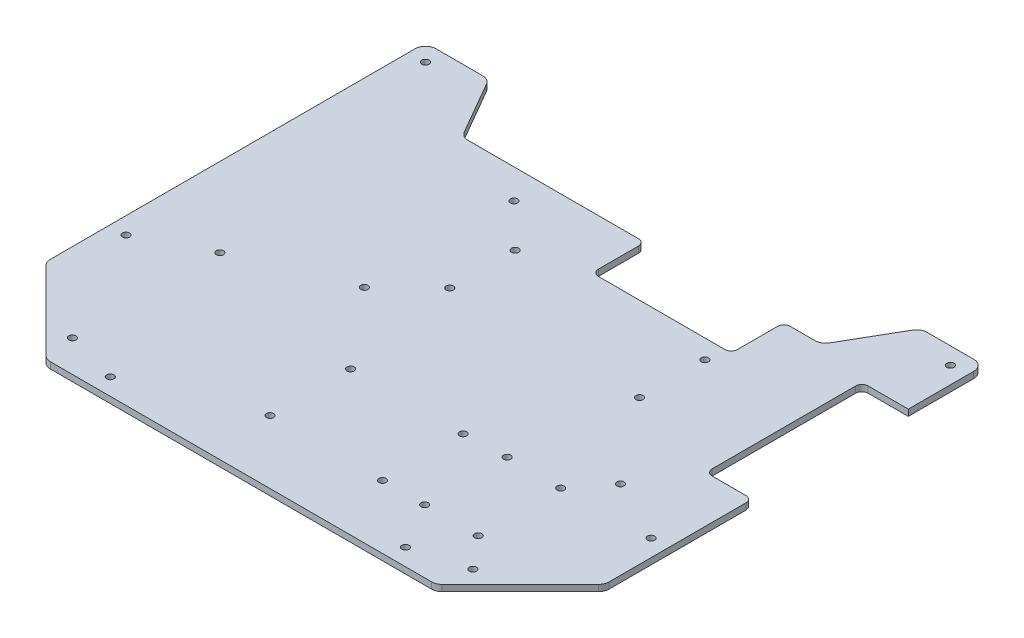
SolidWorks part; units mm, degrees
material "Acier non allié"
ref_plane "Front" through (0, 0, 0) normal (0, 0, 1) x (1, 0, 0)
ref_plane "Top" through (0, 0, 0) normal (0, 1, 0) x (1, 0, 0)
ref_plane "Right" through (0, 0, 0) normal (1, 0, 0) x (0, 0, -1)
sketch "Esquisse1" plane through (0, 0, 0) normal (0, 1, 0) x (1, 0, 0)
  line L0 (0, 0) -> (0, 190) construction
  line L1 (-92.5, 0) -> (92.5, 0)
  line L2 (92.5, 0) -> (132.5, 40)
  line L3 (132.5, 40) -> (132.5, 220)
  line L4 (132.5, 220) -> (102.5, 220)
  line L5 (102.5, 220) -> (85.1795, 190)
  line L6 (85.1795, 190) -> (-85.1795, 190)
  line L7 (-102.5, 220) -> (-85.1795, 190)
  line L8 (-132.5, 220) -> (-102.5, 220)
  line L9 (-132.5, 40) -> (-132.5, 220)
  line L10 (-92.5, 0) -> (-132.5, 40)
  dimension "D1" = 132.5
  dimension "D2" = 220
  dimension "D3" = 60
  dimension "D4" = 30
  dimension "D5" = 40
  dimension "D6" = 40
  dimension "D7" = 30
extrude "Boss.-Extru.1" add sketch "Esquisse1" along normal blind 3
fillet "Congé1" radius 5 10 edges at (92.5, 1.5, 0) (132.5, 1.5, -40) (132.5, 1.5, -220) (102.5, 1.5, -220) (85.1795, 1.5, -190) (-85.1795, 1.5, -190) (-102.5, 1.5, -220) (-132.5, 1.5, -220) (-92.5, 1.5, 0) (-132.5, 1.5, -40)
sketch "Esquisse2" plane through (0, 3, 0) normal (0, 1, 0) x (1, 0, 0)
  line L0 (0, 0) -> (0, 294.1173) construction
  line L2 (-90.4289, 0) -> (90.4289, 0) construction
  circle A0 centre (70, 8) radius 1
  circle A1 centre (124.5, 70) radius 1
  circle A2 centre (124.5, 212) radius 1
  circle A3 centre (-124.5, 212) radius 1
  circle A4 centre (-124.5, 70) radius 1
  circle A5 centre (-70, 8) radius 1
  dimension "D2" = 2
  dimension "D6" = 2
  dimension "D9" = 2
  dimension "D1" = 70
  dimension "D3" = 8
  dimension "D4" = 124.5
  dimension "D5" = 70
  dimension "D7" = 124.5
  dimension "D8" = 212
extrude "Enlèv. mat.-Extru.1" cut sketch "Esquisse2" against normal blind 3
hole_wizard "Dégagement M31" positions "Esquisse3" profile "Esquisse4" hole size "M3" standard "ISO" end condition through all
sketch "Esquisse3" plane through (0, 3, 0) normal (0, 1, 0) x (1, 0, 0)
  point P0 (70, 8)
  point P3 (-70, 8)
  point P6 (-124.5, 70)
  point P9 (-124.5, 212)
  point P12 (124.5, 212)
  point P15 (124.5, 70)
sketch "Esquisse4" plane through (70, 3, -8) normal (1, 0, 0) x (0, 0, 1)
  line L0 (0, 0) -> (0, 3)
  line L1 (0, 3) -> (1.7, 3)
  line L2 (1.7, 3) -> (1.7, 0)
  line L5 (1.7, 0) -> (0, 0)
  line L11 (0, -6.35) -> (0, 107.95) construction
  dimension "Diamètre du perçage jusqu'au prochain" = 3.4
  dimension "Profondeur du perçage jusqu'au prochain" = 3
sketch "Esquisse5" plane through (0, 3, 0) normal (0, 1, 0) x (1, 0, 0)
  line L0 (82.2927, 190) -> (-82.2927, 190) construction
  line L1 (67.5, 190) -> (1.5, 190)
  line L2 (67.5, 190) -> (67.5, 165)
  line L3 (67.5, 165) -> (1.5, 165)
  line L4 (1.5, 190) -> (1.5, 165)
  line L5 (132.5, 42.0711) -> (132.5, 215) construction
  line L6 (132.5, 184) -> (110.5, 184)
  line L7 (132.5, 184) -> (132.5, 110)
  line L8 (132.5, 110) -> (110.5, 110)
  line L9 (110.5, 184) -> (110.5, 110)
  line L10 (127.5, 220) -> (105.3868, 220) construction
  dimension "D1" = 25
  dimension "D2" = 65
  dimension "D3" = 131
  dimension "D4" = 36
  dimension "D5" = 110
  dimension "D6" = 22
extrude "Enlèv. mat.-Extru.2" cut sketch "Esquisse5" against normal through all
fillet "Congé2" radius 3 7 edges at (132.5, 1.5, -110) (110.5, 1.5, -110) (110.5, 1.5, -184) (67.5, 1.5, -190) (67.5, 1.5, -165) (1.5, 1.5, -165) (1.5, 1.5, -190)
sketch "Esquisse6" plane through (0, 3, 0) normal (0, 1, 0) x (1, 0, 0)
  line L0 (110.5, 140.5) -> (-167.6757, 140.5) construction
  line L1 (110.5, 181) -> (110.5, 113) construction
  line L2 (-90.4289, 0) -> (90.4289, 0) construction
  line L3 (110.5, 181) -> (110.5, 113) construction
  circle A0 centre (64, 156) radius 1
  circle A1 centre (-26, 156) radius 1
  circle A2 centre (-46.5, 176) radius 1
  circle A3 centre (64, 125) radius 1
  circle A4 centre (-26, 125) radius 1
  circle A5 centre (-46.5, 105) radius 1
  dimension "D4" = 2
  dimension "D6" = 2
  dimension "D10" = 2
  dimension "D1" = 140.5
  dimension "D2" = 46.5
  dimension "D3" = 15.5
  dimension "D5" = 136.5
  dimension "D7" = 15.5
  dimension "D8" = 35.5
  dimension "D9" = 157
extrude "Enlèv. mat.-Extru.3" cut sketch "Esquisse6" against normal through all
hole_wizard "Dégagement M32" positions "Esquisse7" profile "Esquisse8" hole size "M3" standard "ISO"
sketch "Esquisse7" plane through (0, 3, 0) normal (0, 1, 0) x (1, 0, 0)
  point P0 (-46.5, 105)
  point P3 (-26, 125)
  point P6 (-26, 156)
  point P9 (-46.5, 176)
  point P12 (64, 156)
  point P15 (64, 125)
sketch "Esquisse8" plane through (-46.5, 3, -105) normal (1, 0, 0) x (0, 0, 1)
  line L0 (0, 0) -> (0, 11.0215)
  line L1 (0, 11.0215) -> (1.7, 10)
  line L2 (1.7, 10) -> (1.7, 0)
  line L5 (1.7, 0) -> (0, 0)
  line L10 (0, 11.0215) -> (-1.7, 10) construction
  line L11 (0, -6.35) -> (0, 107.95) construction
  dimension "Diamètre du perçage" = 3.4
  dimension "Profondeur du perçage" = 10
  dimension "Angle de pointe" = 118
sketch "Esquisse9" plane through (0, 3, 0) normal (0, 1, 0) x (1, 0, 0)
  line L0 (132.5, 42.0711) -> (132.5, 107) construction
  line L1 (-90.4289, 0) -> (90.4289, 0) construction
  line L3 (37.1, 30) -> (-16.24, 30) construction
  line L4 (37.1, 30) -> (37.1, 68.24) construction
  line L5 (37.1, 68.24) -> (-16.24, 68.24) construction
  line L6 (-16.24, 30) -> (-16.24, 68.24) construction
  circle A0 centre (82.5, 30) radius 1
  circle A1 centre (57.1, 30) radius 1
  circle A2 centre (57.1, 69.12) radius 1
  circle A3 centre (82.5, 69.12) radius 1
  circle A6 centre (-16.24, 68.24) radius 1
  circle A7 centre (37.1, 68.24) radius 1
  circle A8 centre (37.1, 30) radius 1
  circle A9 centre (-16.24, 30) radius 1
  dimension "D1" = 2
  dimension "D2" = 2
  dimension "D3" = 2
  dimension "D4" = 2
  dimension "D17" = 2
  dimension "D18" = 2
  dimension "D19" = 2
  dimension "D20" = 2
  dimension "D5" = 50
  dimension "D6" = 50
  dimension "D7" = 25.4
  dimension "D8" = 25.4
  dimension "D9" = 39.12
  dimension "D10" = 39.12
  dimension "D11" = 30
  dimension "D12" = 30
  dimension "D13" = 38.24
  dimension "D14" = 53.34
  dimension "D15" = 30
  dimension "D16" = 20
extrude "Enlèv. mat.-Extru.4" cut sketch "Esquisse9" against normal through all
hole_wizard "Dégagement M33" positions "Esquisse10" profile "Esquisse11" hole size "M3" standard "ISO"
sketch "Esquisse10" plane through (0, 3, 0) normal (0, 1, 0) x (1, 0, 0)
  point P0 (57.1, 30)
  point P3 (82.5, 30)
  point P6 (57.1, 69.12)
  point P9 (82.5, 69.12)
sketch "Esquisse11" plane through (57.1, 3, -30) normal (1, 0, 0) x (0, 0, 1)
  line L0 (0, 0) -> (0, 11.0215)
  line L1 (0, 11.0215) -> (1.7, 10)
  line L2 (1.7, 10) -> (1.7, 0)
  line L5 (1.7, 0) -> (0, 0)
  line L10 (0, 11.0215) -> (-1.7, 10) construction
  line L11 (0, -6.35) -> (0, 107.95) construction
  dimension "Diamètre du perçage" = 3.4
  dimension "Profondeur du perçage" = 10
  dimension "Angle de pointe" = 118
sketch "Esquisse12" plane through (0, 3, 0) normal (0, 1, 0) x (1, 0, 0)
  line L2 (-90.4289, 0) -> (90.4289, 0) construction
  line L3 (95, 15) -> (-95, 15) construction
  line L4 (95, 15) -> (95, 85) construction
  line L5 (95, 85) -> (-95, 85) construction
  line L6 (-95, 15) -> (-95, 85) construction
  line L7 (132.5, 42.0711) -> (132.5, 107) construction
  circle A4 centre (-95, 85) radius 1
  circle A5 centre (95, 85) radius 1
  circle A6 centre (95, 15) radius 1
  circle A7 centre (-95, 15) radius 1
  point P6 (95, 50)
  dimension "D5" = 2
  dimension "D6" = 2
  dimension "D7" = 2
  dimension "D8" = 2
  dimension "D1" = 70
  dimension "D2" = 190
  dimension "D3" = 15
  dimension "D4" = 37.5
extrude "Enlèv. mat.-Extru.5" cut sketch "Esquisse12" against normal through all and the other way through all
hole_wizard "Dégagement M34" positions "Esquisse13" profile "Esquisse14" hole size "M3" standard "ISO"
sketch "Esquisse13" plane through (0, 3, 0) normal (0, 1, 0) x (1, 0, 0)
  point P3 (-16.24, 68.24)
  point P6 (-16.24, 30)
  point P9 (37.1, 30)
  point P12 (37.1, 68.24)
sketch "Esquisse14" plane through (-16.24, 3, -68.24) normal (1, 0, 0) x (0, 0, 1)
  line L0 (0, 0) -> (0, 11.0215)
  line L1 (0, 11.0215) -> (1.7, 10)
  line L2 (1.7, 10) -> (1.7, 0)
  line L5 (1.7, 0) -> (0, 0)
  line L10 (0, 11.0215) -> (-1.7, 10) construction
  line L11 (0, -6.35) -> (0, 107.95) construction
  dimension "Diamètre du perçage" = 3.4
  dimension "Profondeur du perçage" = 10
  dimension "Angle de pointe" = 118
hole_wizard "Dégagement M35" positions "Esquisse15" profile "Esquisse16" hole size "M3" standard "ISO"
sketch "Esquisse15" plane through (0, 3, 0) normal (0, 1, 0) x (1, 0, 0)
  point P0 (-95, 15)
  point P3 (-95, 85)
  point P6 (95, 85)
  point P9 (95, 15)
sketch "Esquisse16" plane through (-95, 3, -15) normal (1, 0, 0) x (0, 0, 1)
  line L0 (0, 0) -> (0, 11.0215)
  line L1 (0, 11.0215) -> (1.7, 10)
  line L2 (1.7, 10) -> (1.7, 0)
  line L5 (1.7, 0) -> (0, 0)
  line L10 (0, 11.0215) -> (-1.7, 10) construction
  line L11 (0, -6.35) -> (0, 107.95) construction
  dimension "Diamètre du perçage" = 3.4
  dimension "Profondeur du perçage" = 10
  dimension "Angle de pointe" = 118
equation "\"WIDTH\"= 300mm'Total width of the robot"
equation "\"LENGTH\"= 220mm'Total length of the robot"
equation "\"CUT_DEPTH\"= 45mm'Depth of the cut on the edges of the plate"
equation "\"Plate_th\"= 3mm'Thickness of the plate"
equation "\"D1\"= \"Plate_th\""
